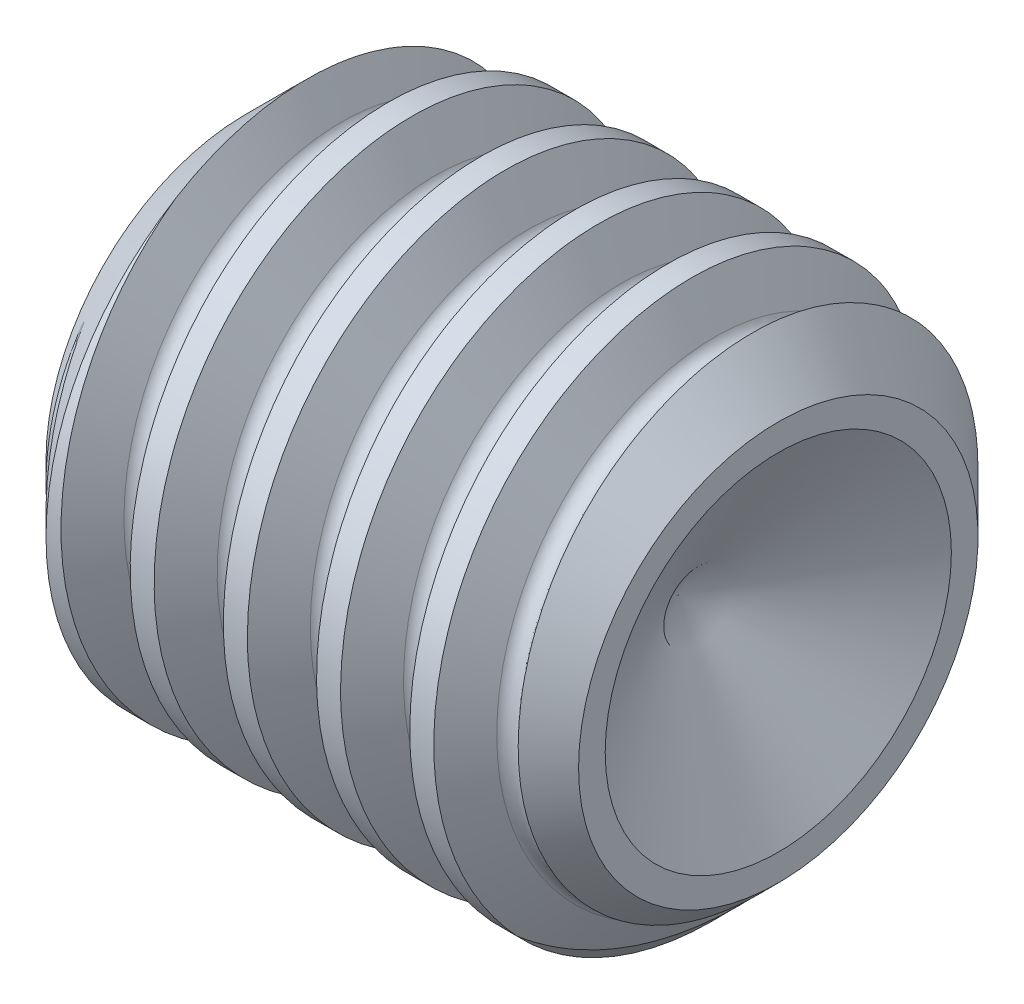
SolidWorks part; units mm, degrees
material "Легированная сталь"
ref_plane "Спереди  XY" through (0, 0, 0) normal (0, 0, 1) x (1, 0, 0)
ref_plane "Сверху  XZ" through (0, 0, 0) normal (0, 1, 0) x (1, 0, 0)
ref_plane "Справа  ZY" through (0, 0, 0) normal (1, 0, 0) x (0, 0, -1)
sketch "Эскиз1" plane through (0, 0, 0) normal (0, 0, 1) x (1, 0, 0)
  line L0 (2, 0) -> (3.2494, 0)
  line L1 (3.2494, 0) -> (4, 1.3)
  line L2 (4, 1.3) -> (4, 1.5)
  line L3 (3.5, 2) -> (0.5, 2)
  line L4 (0, 1.5) -> (0, 1.2)
  line L5 (0.2, 1) -> (1.567, 1)
  line L7 (2, 0) -> (2, 0.25)
  line L8 (2, 0.25) -> (1.567, 1)
  line L9 (4, 1.5) -> (3.5, 2)
  line L10 (0.5, 2) -> (0, 1.5)
  line L11 (0, 1.2) -> (0.2, 1)
  point P0 (0, 0)
  point P3 (0, 1)
  point P5 (4, 2)
  point P6 (0, 2)
  dimension "D1" = 4
  dimension "D2" = 2
  dimension "D3" = 0.25
  dimension "D4" = 60
  dimension "D5" = 1
  dimension "D6" = 60
  dimension "D7" = 2
  dimension "D8" = 1.3
revolve "Повернуть1" add sketch "Эскиз1" angle 360 about L0
sketch "Эскиз2" plane through (0, 0, 0) normal (-1, 0, 0) x (0, 0, 1)
  line L0 (0, 1) -> (0, 0) construction
  line L1 (-0.5774, 1) -> (-1.1547, 0)
  line L2 (-1.1547, 0) -> (-0.5774, -1)
  line L3 (-0.5774, -1) -> (0.5774, -1)
  line L4 (0.5774, -1) -> (1.1547, 0)
  line L5 (1.1547, 0) -> (0.5774, 1)
  line L6 (0.5774, 1) -> (-0.5774, 1)
  circle A0 centre (0, 0) radius 1 construction
  dimension "D1" = 1
extrude "Вырез-Вытянуть1" cut sketch "Эскиз2" against normal blind 1.6
sketch "Эскиз3" plane through (0, 0, 0) normal (-1, 0, 0) x (0, 0, 1)
  circle A0 centre (0, 0) radius 2 construction
  circle A1 centre (0, 0) radius 2
curve "Спираль1" pitch 0.7 height 4.2 radius 2 centre (0, 0, 0) axis (1, 0, 0) start towards (0, 0, -1)
sketch "Эскиз4" plane through (0, 0, 0) normal (0, 0, 1) x (1, 0, 0)
  line L0 (0, 0) -> (0, 2) construction
  line L1 (0.2598, 2) -> (-0.2598, 2)
  line L2 (-0.2598, 2) -> (-0.0866, 1.7)
  line L3 (0.2598, 2) -> (0.0866, 1.7)
  arc A0 (-0.0866, 1.7) -> (0.0866, 1.7) centre (0, 1.75) ccw
  point P8 (0, 1.55)
  dimension "D3" = 0.1
  dimension "D4" = 0.25
  dimension "D1" = 2
  dimension "D2" = 60
sweep "Вырез-По траектории1" cut profiles "Эскиз4" path "Спираль1" align with end faces yes
